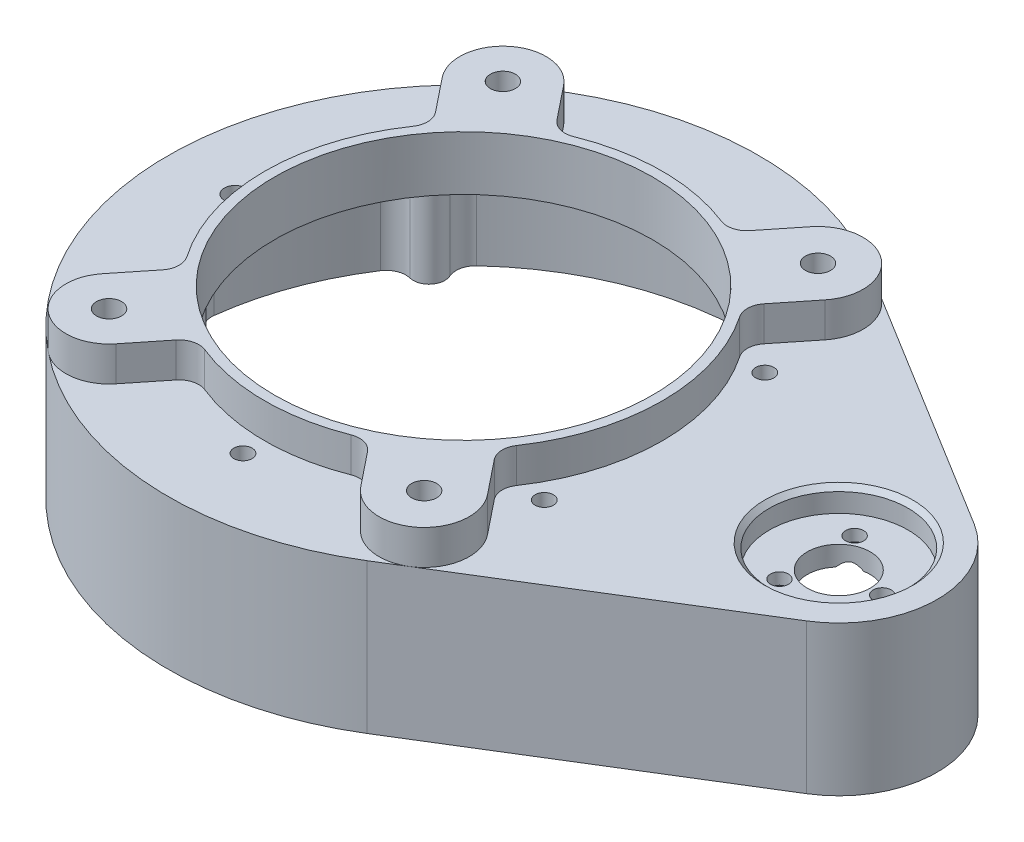
SolidWorks part; units mm, degrees
material "6061-T6 (SS)"
ref_plane "Front Plane" through (0, 0, 0) normal (0, 0, 1) x (1, 0, 0)
ref_plane "Top Plane" through (0, 0, 0) normal (0, 1, 0) x (1, 0, 0)
ref_plane "Right Plane" through (0, 0, 0) normal (1, 0, 0) x (0, 0, -1)
sketch "Sketch1" plane through (0, 0, 0) normal (0, 1, 0) x (1, 0, 0)
  circle A0 centre (0, 0) radius 47.625
  dimension "D1" = 95.25
extrude "Boss-Extrude1" add sketch "Sketch1" along normal blind 24.13
sketch "Sketch2" plane through (0, 0, 0) normal (0, -1, 0) x (1, 0, 0)
  circle A0 centre (0, 0) radius 46.0375
  circle A1 centre (0, 0) radius 47.625 construction
  dimension "D1" = 1.5875
extrude "Cut-Extrude1" cut sketch "Sketch2" against normal offset from surface (20.955 mm away) 3.175 up to face at (0, 24.13, 47.625)
sketch "Sketch3" plane through (0, 20.955, 0) normal (0, -1, 0) x (1, 0, 0)
  circle A0 centre (0, 0) radius 30.48
  dimension "D1" = 60.96
extrude "Cut-Extrude2" cut sketch "Sketch3" against normal through all
sketch "Sketch4" plane through (0, 24.13, 0) normal (0, 1, 0) x (1, 0, 0)
  line L0 (24.9921, 40.5405) -> (68.8335, 13.5135)
  line L1 (24.9921, -40.5405) -> (68.8335, -13.5135)
  arc A0 (68.8335, -13.5135) -> (68.8335, 13.5135) centre (60.5028, 0) ccw
  circle A1 centre (0, 0) radius 47.625 construction
  arc A2 (24.9921, -40.5405) -> (24.9921, 40.5405) centre (0, 0) ccw
  dimension "D2" = 31.75
  dimension "D1" = 60.5028
extrude "Boss-Extrude2" add sketch "Sketch4" against normal up to surface (24.13 mm away) up to face at (0, 0, -46.0375)
sketch "Sketch5" plane through (0, 0, 0) normal (0, -1, 0) x (1, 0, 0)
  line L4 (24.1591, -39.1892) -> (68.0004, -12.1622)
  line L5 (68.0004, 12.1622) -> (24.1591, 39.1892)
  line L6 (24.1591, -39.1892) -> (68.0004, -12.1622)
  line L7 (68.0004, 12.1622) -> (24.1591, 39.1892)
  circle A1 centre (0, 0) radius 46.0375 construction
  arc A2 (68.0004, -12.1622) -> (68.0004, 12.1622) centre (60.5028, 0) ccw
  arc A3 (68.0004, -12.1622) -> (68.0004, 12.1622) centre (60.5028, 0) ccw
  arc A4 (24.1591, -39.1892) -> (24.1591, 39.1892) centre (0, 0) ccw
  dimension "D1" = 1.5875
extrude "Cut-Extrude3" cut sketch "Sketch5" against normal up to surface (20.955 mm away) up to face at (0, 20.955, -30.48)
sketch "Sketch6" plane through (0, 20.955, 0) normal (0, -1, 0) x (1, 0, 0)
  line L0 (68.0004, 12.1622) -> (24.1591, 39.1892) construction
  line L1 (24.1591, -39.1892) -> (68.0004, -12.1622) construction
  line L2 (53.2589, 21.2499) -> (46.0797, 25.6757)
  line L3 (46.0797, -25.6757) -> (53.2589, -21.2499)
  line L4 (68.8335, 13.5135) -> (24.9921, 40.5405) construction
  line L5 (24.9921, -40.5405) -> (68.8335, -13.5135) construction
  line L6 (68.8335, 13.5135) -> (46.9128, 27.027)
  line L7 (46.9128, -27.027) -> (68.8335, -13.5135)
  line L8 (46.0797, 25.6757) -> (46.9128, 27.027)
  line L9 (46.9128, -27.027) -> (46.0797, -25.6757)
  arc A0 (53.452, 10.563) -> (53.452, -10.563) centre (60.5028, 0) ccw
  arc A2 (68.8335, -13.5135) -> (68.8335, 13.5135) centre (60.5028, 0) ccw construction
  arc A3 (68.8335, -13.5135) -> (68.8335, 13.5135) centre (60.5028, 0) ccw
  arc A4 (53.2589, -21.2499) -> (53.452, -10.563) centre (49.9267, -15.8445) ccw
  arc A5 (53.2589, 21.2499) -> (53.452, 10.563) centre (49.9267, 15.8445) cw
  dimension "D1" = 6.35
  dimension "D2" = 12.7
extrude "Boss-Extrude3" add sketch "Sketch6" along normal blind 3.81
sketch "Sketch7" plane through (0, 24.13, 0) normal (0, 1, 0) x (1, 0, 0)
  circle A0 centre (60.5028, 0) radius 11.176
  dimension "D1" = 22.352
extrude "Cut-Extrude4" cut sketch "Sketch7" against normal blind 3.81
chamfer "Chamfer1" distance 0.762 angle 45 1 edges at (60.5028, 24.13, 11.176)
sketch "Sketch8" plane through (0, 20.32, 0) normal (0, 1, 0) x (1, 0, 0)
  circle A0 centre (60.5028, 0) radius 5.08
  dimension "D1" = 10.16
extrude "Cut-Extrude5" cut sketch "Sketch8" against normal through all
hole_wizard "CSK for M2.5 Flat Head Machine Screw1" positions "Sketch10" profile "Sketch9" countersink size "M2.5" standard "Ansi Metric" end condition through all
sketch "Sketch10" plane through (0, 17.145, 0) normal (0, -1, 0) x (1, 0, 0)
  line L0 (60.5028, 0) -> (76.3778, 0) construction
  arc A0 (68.8335, -13.5135) -> (68.8335, 13.5135) centre (60.5028, 0) ccw construction
  point P0 (67.5028, 0)
  dimension "D1" = 7
sketch "Sketch9" plane through (67.5028, 17.145, 0) normal (1, 0, 0) x (0, 0, -1)
  line L0 (0, 0) -> (0, 6.985)
  line L1 (0, 6.985) -> (1.45, 6.985)
  line L2 (1.45, 6.985) -> (1.45, 1.3)
  line L3 (1.45, 1.3) -> (2.75, 0)
  line L5 (2.75, 0) -> (0, 0)
  line L6 (-1.45, 1.3) -> (-2.75, 0) construction
  line L11 (0, -6.35) -> (0, 107.95) construction
  dimension "Thru Hole Dia." = 2.9
  dimension "Thru Hole Depth" = 6.985
  dimension "Near C'Sink Dia." = 5.5
  dimension "Near C'Sink Angle" = 90
pattern_circular "CirPattern1" count 3 over 360 about axis through (60.5028, 17.145, 0) along (0, -1, 0) of "CSK for M2.5 Flat Head Machine Screw1"
sketch "Sketch11" plane through (0, 24.13, 0) normal (0, 1, 0) x (1, 0, 0)
  line L0 (68.8335, 13.5135) -> (24.9921, 40.5405) construction
  line L1 (-25.4, -31.75) -> (25.4, -31.75) construction
  line L2 (-25.4, -31.75) -> (-25.4, -16.8485) construction
  line L3 (-25.4, 31.75) -> (25.4, 31.75) construction
  line L4 (25.4, -31.75) -> (25.4, 31.75) construction
  line L5 (-25.4, -31.75) -> (25.4, 31.75) construction
  line L6 (-25.4, 31.75) -> (25.4, -31.75) construction
  line L7 (-30.8389, 27.3989) -> (-23.9758, 18.82)
  line L8 (-19.9611, 36.1011) -> (-13.098, 27.5222)
  line L9 (19.724, 36.2908) -> (12.8153, 27.655)
  line L10 (31.076, 27.2092) -> (24.1674, 18.5734)
  line L11 (-25.4, 16.8485) -> (-25.4, 31.75) construction
  arc A0 (-19.9611, 36.1011) -> (-30.8389, 27.3989) centre (-25.4, 31.75) ccw
  arc A3 (24.9921, 40.5405) -> (24.9921, -40.5405) centre (0, 0) ccw construction
  arc A4 (31.076, 27.2092) -> (19.724, 36.2908) centre (25.4, 31.75) ccw
  circle A6 centre (0, 0) radius 30.48 construction
  arc A7 (-13.098, 27.5222) -> (-23.9758, 18.82) centre (0, 0) ccw
  arc A8 (24.1674, 18.5734) -> (12.8153, 27.655) centre (0, 0) ccw
  point P0 (0, 0)
  dimension "D1" = 50.8
  dimension "D2" = 63.5
extrude "Boss-Extrude4" add sketch "Sketch11" along normal blind 5.588
mirror "Mirror1" about plane through (0, 0, 0) normal (0, 0, 1) of "Boss-Extrude4"
sketch "Sketch12" plane through (0, 24.13, 0) normal (0, 1, 0) x (1, 0, 0)
  circle A1 centre (0, 0) radius 30.48
  arc A2 (12.8153, 27.655) -> (-13.098, 27.5222) centre (0, 0) ccw construction
  circle A3 centre (0, 0) radius 32.0675
  dimension "D1" = 1.5875
extrude "Boss-Extrude5" add sketch "Sketch12" along normal up to surface (5.588 mm away) up to face at (-23.1822, 29.718, -28.9777)
fillet "Fillet2" radius 3.175 8 edges at (-24.993, 26.924, 20.0916) (-14.1153, 26.924, 28.7938) (13.835, 26.924, 28.9295) (25.187, 26.924, 19.8479) (25.187, 26.924, -19.8479) (13.835, 26.924, -28.9295) (-14.1153, 26.924, -28.7938) (-24.993, 26.924, -20.0916)
hole_wizard "#10-32 Tapped Hole1" positions "Sketch14" profile "Sketch15" tap size "#10-32" standard "Ansi Inch" end condition up to next
sketch "Sketch14" plane through (0, 29.718, 0) normal (0, 1, 0) x (-1, 0, 0)
  point P0 (25.4, -31.75)
  point P1 (-25.4, -31.75)
  point P4 (25.4, 31.75)
  point P7 (-25.4, 31.75)
sketch "Sketch15" plane through (-25.4, 29.718, -31.75) normal (1, 0, 0) x (0, 0, 1)
  line L0 (0, 0) -> (0, 8.763)
  line L1 (0, 8.763) -> (2.0193, 8.763)
  line L2 (2.0193, 8.763) -> (2.0193, 0)
  line L5 (2.0193, 0) -> (0, 0)
  line L11 (0, -6.35) -> (0, 107.95) construction
  dimension "Thru Tap Drill Dia." = 4.0386
  dimension "Thru Tap Drill Depth" = 8.763
cosmetic thread "Hole Thread1" parameters "D2"=4.826
cosmetic thread "Hole Thread2" parameters "D2"=4.826
cosmetic thread "Hole Thread3" parameters "D2"=4.826
cosmetic thread "Hole Thread4" parameters "D2"=4.826
hole_wizard "#4 Clearance Hole1" positions "Sketch18" profile "Sketch17" hole size "#4" standard "Ansi Inch"
sketch "Sketch18" plane through (0, 24.13, 0) normal (0, 1, 0) x (-1, 0, 0)
  point P0 (0, -35.56)
  dimension "D1" = 35.56
sketch "Sketch17" plane through (0, 24.13, -35.56) normal (1, 0, 0) x (0, 0, 1)
  line L0 (0, 0) -> (0, 83.9432)
  line L1 (0, 83.9432) -> (1.4732, 83.058)
  line L2 (1.4732, 83.058) -> (1.4732, 0)
  line L5 (1.4732, 0) -> (0, 0)
  line L10 (0, 83.9432) -> (-1.4732, 83.058) construction
  line L11 (0, -6.35) -> (0, 107.95) construction
  dimension "Hole Dia." = 2.9464
  dimension "Hole Depth" = 83.058
  dimension "Drill Angle" = 118
pattern_circular "CirPattern2" count 6 over 360 about axis through (0, 29.718, 0) along (0, -1, 0) of "#4 Clearance Hole1"
sketch "Sketch19" plane through (0, 0, 0) normal (0, -1, 0) x (1, 0, 0)
  line L0 (68.8335, 13.5135) -> (24.9921, 40.5405) construction
  line L1 (-34.5371, 28.9801) -> (0, 0) construction
  line L2 (0, 0) -> (22.5425, 39.0448) construction
  line L3 (0, 0) -> (66.8058, 11.7797) construction
  line L4 (0, 0) -> (76.3778, 0) construction
  circle A0 centre (-45.085, 0) radius 2.54
  arc A1 (24.9921, 40.5405) -> (24.9921, -40.5405) centre (0, 0) ccw construction
  circle A2 centre (-34.5371, 28.9801) radius 2.54
  circle A3 centre (66.8058, 11.7797) radius 2.54
  circle A4 centre (22.5425, 39.0448) radius 2.54
  arc A5 (68.8335, -13.5135) -> (68.8335, 13.5135) centre (60.5028, 0) ccw construction
  circle A6 centre (66.8058, -11.7797) radius 2.54
  circle A7 centre (22.5425, -39.0448) radius 2.54
  circle A8 centre (-34.5371, -28.9801) radius 2.54
  dimension "D1" = 5.08
  dimension "D2" = 10
  dimension "D3" = 60
  dimension "D4" = 140
extrude "Boss-Extrude6" add sketch "Sketch19" against normal up to surface (20.955 mm away) up to face at (-30.7959, 20.955, -16.3068)
fillet "Fillet3" radius 3.175 14 edges at (20.9281, 10.4775, 41.0057) (25.05, 10.4775, 38.6399) (65.3013, 8.5725, 13.8261) (69.2928, 8.5725, 11.2636) (69.2928, 8.5725, -11.2636) (65.3013, 8.5725, -13.8261) (25.05, 10.4775, -38.6399) (20.9281, 10.4775, -41.0057) (-33.6907, 10.4775, -31.3749) (-36.7486, 10.4775, -27.7307) (-45.976, 10.4775, -2.3786) (-45.976, 10.4775, 2.3786) (-33.6907, 10.4775, 31.3749) (-36.7486, 10.4775, 27.7307)
hole_wizard "#2-56 Tapped Hole1" positions "Sketch21" profile "Sketch20" tap size "#2-56" standard "Ansi Inch"
sketch "Sketch21" plane through (0, 0, 0) normal (0, -1, 0) x (1, 0, 0)
  point P0 (-34.5371, 28.9801)
  point P1 (22.5425, 39.0448)
  point P4 (66.8058, 11.7797)
  point P7 (66.8058, -11.7797)
  point P10 (22.5425, -39.0448)
  point P13 (-34.5371, -28.9801)
  point P16 (-45.085, 0)
sketch "Sketch20" plane through (-34.5371, 0, 28.9801) normal (1, 0, 0) x (0, 0, -1)
  line L0 (0, 0) -> (0, 6.1222)
  line L1 (0, 6.1222) -> (0.889, 5.588)
  line L2 (0.889, 5.588) -> (0.889, 0)
  line L5 (0.889, 0) -> (0, 0)
  line L10 (0, 6.1222) -> (-0.889, 5.588) construction
  line L11 (0, -6.35) -> (0, 107.95) construction
  dimension "Tap Drill Dia." = 1.778
  dimension "Tap Drill Depth" = 5.588
  dimension "Drill Angle" = 118
cosmetic thread "Hole Thread5" parameters "D1"=4.318, "D2"=2.1844
cosmetic thread "Hole Thread6" parameters "D1"=4.318, "D2"=2.1844
cosmetic thread "Hole Thread7" parameters "D1"=4.318, "D2"=2.1844
cosmetic thread "Hole Thread8" parameters "D1"=4.318, "D2"=2.1844
cosmetic thread "Hole Thread9" parameters "D1"=4.318, "D2"=2.1844
cosmetic thread "Hole Thread10" parameters "D1"=4.318, "D2"=2.1844
cosmetic thread "Hole Thread11" parameters "D1"=4.318, "D2"=2.1844
sketch "Sketch23" plane through (0, 17.145, 0) normal (0, -1, 0) x (1, 0, 0)
  line L0 (47.8028, 0) -> (47.8028, 24.6135)
  line L1 (53.2589, 21.2499) -> (27.5408, 37.1044) construction
  line L2 (62.8237, 15.3535) -> (27.5408, 37.1044) construction
  line L3 (53.2589, 21.2499) -> (47.8028, 24.6135)
  arc A0 (53.452, 10.563) -> (53.452, -10.563) centre (60.5028, 0) ccw construction
  arc A1 (53.452, 10.563) -> (53.2589, 21.2499) centre (49.9267, 15.8445) ccw construction
  arc A2 (53.452, 10.563) -> (53.2589, 21.2499) centre (49.9267, 15.8445) ccw
  arc A3 (53.452, 10.563) -> (47.8028, 0) centre (60.5028, 0) ccw
extrude "Boss-Extrude7" add sketch "Sketch23" against normal up to surface (3.81 mm away) up to face at (-30.7959, 20.955, -16.3068)
fillet "Fillet4" radius 6.35 1 edges at (47.8028, 19.05, 24.6135)
sketch "Sketch22" plane through (0, 20.955, 0) normal (0, -1, 0) x (1, 0, 0)
  line L0 (20.0752, 32.4731) -> (63.8486, 5.412)
  line L1 (20.0752, -32.4731) -> (63.8486, -5.412)
  arc A0 (20.0752, 32.4731) -> (20.0752, -32.4731) centre (0, 0) ccw
  arc A1 (63.8486, -5.412) -> (63.8486, 5.412) centre (60.5028, 0) ccw
  circle A2 centre (52.8828, 15.1773) radius 3.175
  dimension "D1" = 76.3549
  dimension "D2" = 12.7254
  dimension "D3" = 6.35
  dimension "D4" = 7.62
  dimension "D5" = 2.54
sketch "Sketch27" plane through (0, 20.32, 0) normal (0, 1, 0) x (1, 0, 0)
  circle A0 centre (60.5028, 0) radius 11.176
  arc A1 (64.7014, 10.3574) -> (64.7014, -10.3574) centre (60.5028, 0) ccw construction
extrude "Cut-Extrude6" cut sketch "Sketch27" along normal up to surface (3.81 mm away) up to face at (-30.7959, 24.13, -16.3068)
hole_wizard "#8-32 Tapped Hole1" positions "Sketch29" profile "Sketch28" tap size "#8-32" standard "Ansi Inch"
sketch "Sketch29" plane through (0, 24.13, 0) normal (0, 1, 0) x (-1, 0, 0)
  point P0 (36.83, 0)
  dimension "D1" = 36.83
sketch "Sketch28" plane through (-36.83, 24.13, 0) normal (1, 0, 0) x (0, 0, 1)
  line L0 (0, 0) -> (0, 11.7058)
  line L1 (0, 11.7058) -> (1.7272, 10.668)
  line L2 (1.7272, 10.668) -> (1.7272, 0)
  line L5 (1.7272, 0) -> (0, 0)
  line L10 (0, 11.7058) -> (-1.7272, 10.668) construction
  line L11 (0, -6.35) -> (0, 107.95) construction
  dimension "Tap Drill Dia." = 3.4544
  dimension "Tap Drill Depth" = 10.668
  dimension "Drill Angle" = 118
